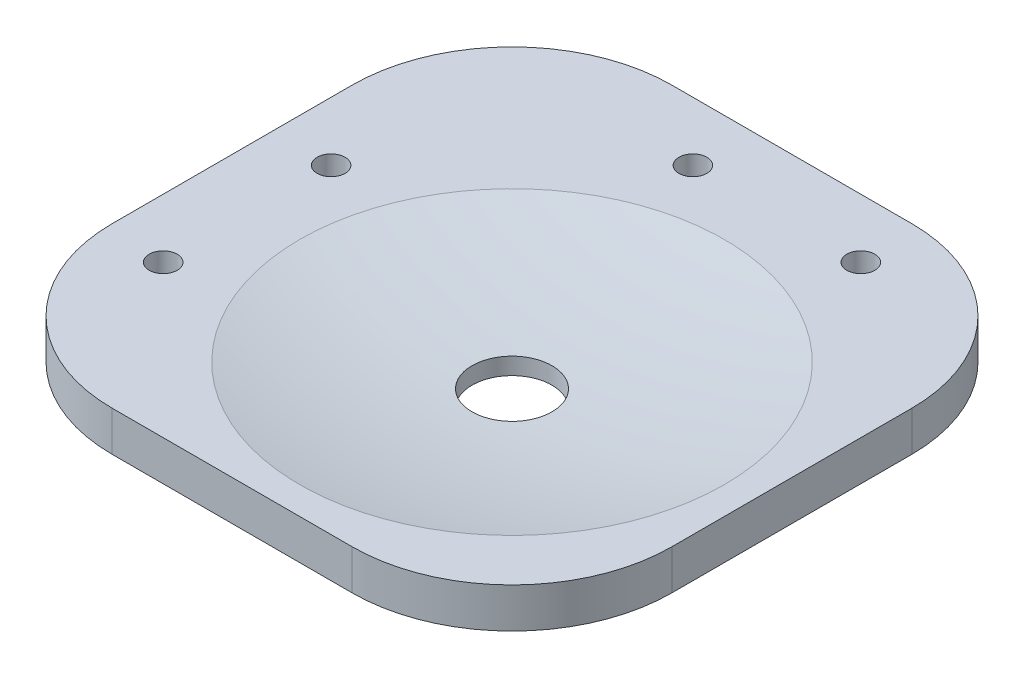
SolidWorks part; units mm, degrees
ref_plane "Front Plane" through (0, 0, 0) normal (0, 0, 1) x (1, 0, 0)
ref_plane "Top Plane" through (0, 0, 0) normal (0, 1, 0) x (1, 0, 0)
ref_plane "Right Plane" through (0, 0, 0) normal (1, 0, 0) x (0, 0, -1)
sketch "Sketch1" plane through (0, 0, 0) normal (0, 1, 0) x (1, 0, 0)
  line L1 (-30, -30) -> (30, -30)
  line L2 (-30, -30) -> (-30, 30)
  line L3 (-30, 30) -> (30, 30)
  line L4 (30, -30) -> (30, 30)
  line L5 (-30, -30) -> (30, 30) construction
  line L6 (-30, 30) -> (30, -30) construction
  point P0 (0, 0)
  dimension "D1" = 60
  dimension "D2" = 60
extrude "Boss-Extrude1" add sketch "Sketch1" along normal blind 5
sketch "Sketch2" plane through (0, 5, 0) normal (0, 1, 0) x (1, 0, 0)
  circle A0 centre (0, 0) radius 5
  dimension "D1" = 10
extrude "Cut-Extrude1" cut sketch "Sketch2" against normal through all
sketch "Sketch3" plane through (0, 0, 0) normal (0, 0, 1) x (1, 0, 0)
  line L0 (0, 2.0073) -> (0, 240.6873)
  arc A0 (0, 2.0073) -> (0, 240.6873) centre (0, 121.3473) ccw
  point P3 (0, 2.0073)
revolve "Cut-Revolve1" cut sketch "Sketch3" angle 360 about L0
sketch "Sketch5" plane through (0, 0, 0) normal (0, 1, 0) x (1, 0, 0)
  line L0 (-30, -30) -> (-40, -30)
  line L1 (-30, 30) -> (-30, -30) construction
  line L2 (-40, -30) -> (-40, 40)
  line L3 (-40, 40) -> (30, 40)
  line L4 (30, 40) -> (30, 30)
  line L5 (30, -30) -> (30, 30) construction
  line L6 (30, 30) -> (-30, 30)
  line L7 (30, 30) -> (-30, 30) construction
  line L8 (-30, 30) -> (-30, -30)
  dimension "D1" = 10
  dimension "D2" = 10
extrude "Boss-Extrude2" add sketch "Sketch5" along normal blind 5
sketch "Sketch4" plane through (0, 5, 0) normal (0, 1, 0) x (1, 0, 0)
  line L0 (-32.6274, 10) -> (-10, 10) construction
  line L3 (-10, 10) -> (-10, 32.6274) construction
  line L4 (-32.6274, 10) -> (-10, 32.6274) construction
  line L7 (-32.6274, -11) -> (-32.6274, 10) construction
  line L8 (-10, 32.6274) -> (11, 32.6274) construction
  line L9 (0, 0) -> (-21.3137, 21.3137) construction
  circle A0 centre (-32.6274, 10) radius 1.75
  circle A1 centre (-10, 32.6274) radius 1.75
  circle A2 centre (11, 32.6274) radius 1.75
  circle A3 centre (-32.6274, -11) radius 1.75
  dimension "D3" = 3.5
  dimension "D2" = 32
  dimension "D4" = 21
  dimension "D5" = 21
  dimension "D6" = 10
  dimension "D7" = 10
extrude "Cut-Extrude2" cut sketch "Sketch4" against normal through all
fillet "Fillet1" radius 20 4 edges at (30, 2.5, 30) (30, 2.5, -40) (-40, 2.5, -40) (-40, 2.5, 30)
